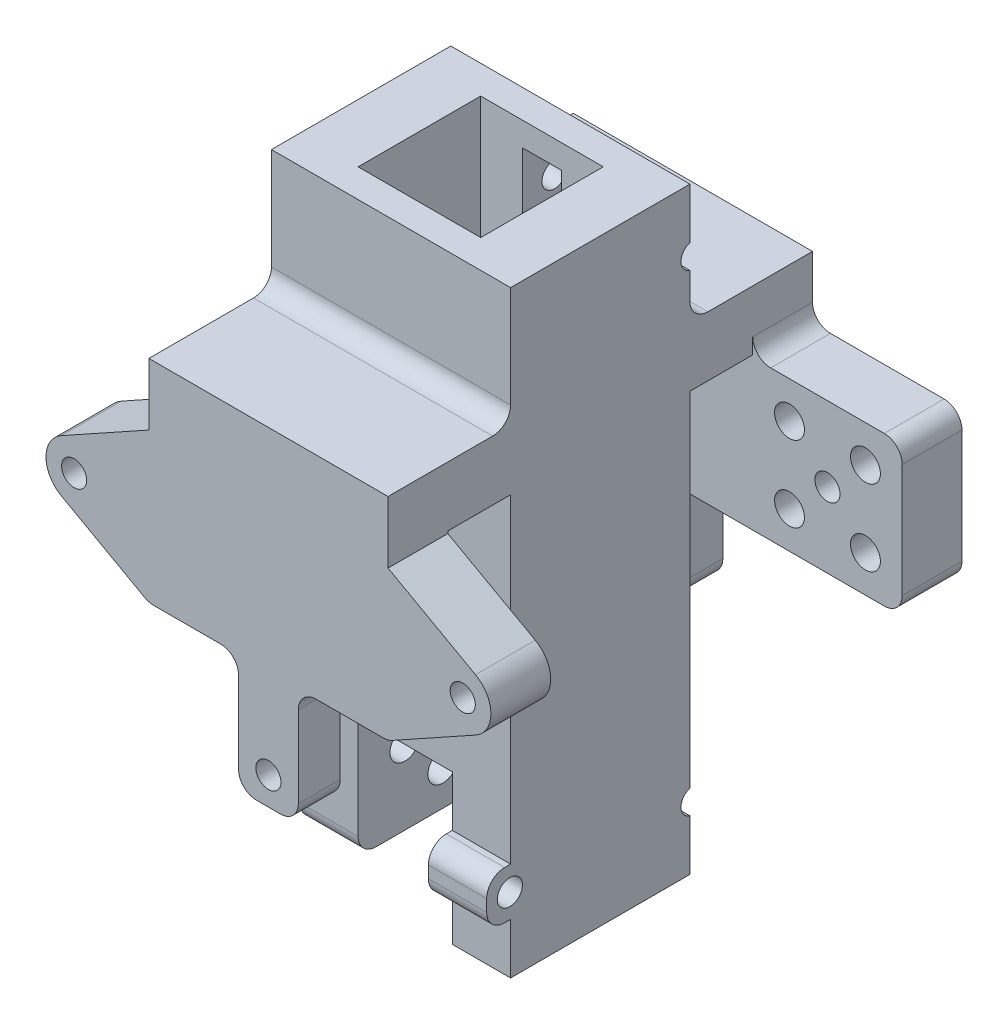
SolidWorks part; units mm, degrees
note: The reader was unsure of these and kept them because the rebuilt part matched: shared geometry of "Sketch25<3>".
ref_plane "Front Plane" through (0, 0, 0) normal (0, 0, 1) x (1, 0, 0)
ref_plane "Top Plane" through (0, 0, 0) normal (0, 1, 0) x (1, 0, 0)
ref_plane "Right Plane" through (0, 0, 0) normal (1, 0, 0) x (0, 0, -1)
sketch "Sketch2" plane through (0, 0, 0) normal (0, 1, 0) x (1, 0, 0)
  line L14 (-20, 15) -> (20, 15)
  line L15 (-20, 15) -> (-20, -15)
  line L16 (-20, -15) -> (20, -15)
  line L17 (20, 15) -> (20, -15)
  line L18 (-20, 15) -> (20, -15) construction
  line L19 (-20, -15) -> (20, 15) construction
  point P0 (0, 0)
  dimension "D1" = 40
  dimension "D2" = 30
extrude "Boss-Extrude1" add sketch "Sketch2" along normal blind 100
sketch "Sketch3" plane through (0, 0, 0) normal (0, 1, 0) x (1, 0, 0)
  line L1 (-10.25, 10.25) -> (10.25, 10.25)
  line L2 (-10.25, 10.25) -> (-10.25, -10.25)
  line L3 (-10.25, -10.25) -> (10.25, -10.25)
  line L4 (10.25, 10.25) -> (10.25, -10.25)
  line L5 (-10.25, 10.25) -> (10.25, -10.25) construction
  line L6 (-10.25, -10.25) -> (10.25, 10.25) construction
  point P0 (0, 0)
  dimension "D1" = 20.5
  dimension "D2" = 20.5
extrude "Cut-Extrude1" cut sketch "Sketch3" along normal blind 100
sketch "Sketch4" plane through (0, 0, 15) normal (0, 0, 1) x (1, 0, 0)
  line L1 (-10.25, -25) -> (10.25, -25)
  line L2 (-10.25, -25) -> (-10.25, 25)
  line L3 (-10.25, 25) -> (10.25, 25)
  line L4 (10.25, -25) -> (10.25, 25)
  line L5 (-10.25, -25) -> (10.25, 25) construction
  line L6 (-10.25, 25) -> (10.25, -25) construction
  point P0 (0, 0)
  dimension "D1" = 20.5
  dimension "D2" = 50
extrude "Cut-Extrude2" cut sketch "Sketch4" against normal up to surface (4.75 mm away) up to face at (0, 50, 10.25)
sketch "Sketch5" plane through (-10.25, 0, 0) normal (1, 0, 0) x (0, 0, -1)
  line L1 (-10.25, 25) -> (-15, 25)
  line L2 (-10.25, 25) -> (-10.25, 0)
  line L3 (-10.25, 0) -> (-15, 0)
  line L4 (-15, 25) -> (-15, 0)
extrude "Cut-Extrude4" cut sketch "Sketch5" against normal up to surface (9.75 mm away) up to face at (-20, 50, 0)
sketch "Sketch6" plane through (-20, 0, 0) normal (-1, 0, 0) x (0, 0, 1)
  line L0 (10.25, 12.5) -> (-15, 12.5) construction
  line L1 (10.25, 25) -> (10.25, 0) construction
  line L2 (-15, 100) -> (-15, 0) construction
  line L4 (10.25, 12.5) -> (15.125, 12.5) construction
  line L5 (-3.925, 12.5) -> (-3.925, 18.85) construction
  circle A0 centre (2.425, 12.5) radius 2.1
  circle A1 centre (-10.275, 12.5) radius 2.1
  circle A2 centre (-3.925, 18.85) radius 2.1
  circle A3 centre (-3.925, 6.15) radius 2.1
  dimension "D2" = 12.7
  dimension "D3" = 4.2
  dimension "D4" = 12.7
  dimension "D5" = 4.2
  dimension "D7" = 6.35
  dimension "D1" = 4.875
  dimension "D6" = 6.35
extrude "Cut-Extrude5" cut sketch "Sketch6" against normal up to surface (9.75 mm away) up to face at (-10.25, 45, 2.05)
sketch "Sketch7" plane through (-10.25, 0, 0) normal (1, 0, 0) x (0, 0, -1)
  circle A0 centre (-2.425, 12.5) radius 2.5
  circle A1 centre (10.275, 12.5) radius 2.5
  circle A2 centre (3.925, 18.85) radius 2.5
  circle A6 centre (3.925, 6.15) radius 2.5
  dimension "D1" = 12.7
extrude "Cut-Extrude6" cut sketch "Sketch7" against normal blind 5.18
sketch "Sketch8" plane through (0, 0, -15) normal (0, 0, -1) x (-1, 0, 0)
  line L0 (-20, 100) -> (-20, 0) construction
  line L1 (20, 100) -> (20, 0) construction
  line L2 (-20, 70) -> (20, 70)
  line L3 (-20, 70) -> (-20, 80)
  line L4 (-20, 80) -> (20, 80)
  line L5 (20, 70) -> (20, 80)
  line L6 (-20, 0) -> (20, 0) construction
  dimension "D1" = 70
  dimension "D2" = 10
extrude "Boss-Extrude2" add sketch "Sketch8" along normal blind 20.5
sketch "Sketch9" plane through (0, 70, 0) normal (0, -1, 0) x (1, 0, 0)
  line L0 (20, -35.5) -> (20, -15) construction
  line L1 (-20, -35.5) -> (20, -35.5)
  line L2 (-20, -35.5) -> (-20, -25.5)
  line L3 (-20, -25.5) -> (20, -25.5)
  line L4 (20, -35.5) -> (20, -25.5)
  dimension "D1" = 10
extrude "Boss-Extrude3" add sketch "Sketch9" along normal blind 45
sketch "Sketch10" plane through (0, 0, -35.5) normal (0, 0, -1) x (-1, 0, 0)
  line L0 (-20, 57.125) -> (20, 57.125) construction
  line L1 (-20, 80) -> (-20, 25) construction
  line L2 (20, 25) -> (20, 80) construction
  line L3 (20, 80) -> (-20, 80) construction
  dimension "D1" = 22.875
sketch "Sketch11" plane through (20, 0, 0) normal (1, 0, 0) x (0, 0, -1)
  line L5 (35.5, 57.125) -> (25.5, 57.125) construction
  line L6 (25.5, 25) -> (25.5, 70) construction
  line L7 (35.5, 80) -> (35.5, 25) construction
  line L8 (25.5, 69.625) -> (35.5, 69.625)
  line L9 (25.5, 69.625) -> (25.5, 44.625)
  line L10 (25.5, 44.625) -> (35.5, 44.625)
  line L11 (35.5, 69.625) -> (35.5, 44.625)
  dimension "D1" = 25
extrude "Boss-Extrude4" add sketch "Sketch11" along normal blind 25 and the other way offset from surface (65 mm away) 25 other way up to face at (-20, 12.5, 4.525)
sketch "Sketch13" plane through (0, 0, -35.5) normal (0, 0, -1) x (-1, 0, 0)
  line L0 (-45, 44.625) -> (-20, 69.625) construction
  line L1 (-20, 44.625) -> (-45, 69.625) construction
  circle A0 centre (-32.5, 57.125) radius 2.1
  circle A1 centre (-26.15, 63.475) radius 2.1
  circle A2 centre (-38.85, 63.475) radius 2.1
  circle A3 centre (-38.85, 50.775) radius 2.1
  circle A4 centre (-26.15, 50.775) radius 2.1
  dimension "D1" = 12.7
  dimension "D2" = 6.35
  dimension "D3" = 12.7
  dimension "D4" = 6.35
extrude "Cut-Extrude7" cut sketch "Sketch13" against normal blind 4.57
sketch "Sketch14" plane through (0, 0, -25.5) normal (0, 0, 1) x (1, 0, 0)
  circle A0 centre (32.5, 57.125) radius 2.1
  circle A1 centre (38.85, 63.475) radius 2.5
  circle A2 centre (26.15, 63.475) radius 2.5
  circle A3 centre (26.15, 50.775) radius 2.5
  circle A4 centre (38.85, 50.775) radius 2.5
extrude "Cut-Extrude8" cut sketch "Sketch14" against normal up to surface (5.43 mm away) up to face at (36.75, 63.475, -30.93)
sketch "Sketch15" plane through (0, 0, -35.5) normal (0, 0, -1) x (-1, 0, 0)
  line L0 (20, 44.625) -> (45, 69.625) construction
  line L1 (45, 44.625) -> (20, 69.625) construction
  line L2 (20, 69.625) -> (34.6326, 61.4958)
  line L3 (34.6326, 52.7542) -> (20, 44.625)
  line L4 (20, 44.625) -> (45, 44.625)
  line L5 (45, 44.625) -> (45, 69.625)
  line L6 (45, 69.625) -> (20, 69.625)
  line L7 (-20, 57.125) -> (20, 57.125) construction
  circle A0 centre (32.5, 57.125) radius 2.1
  arc A1 (34.6326, 52.7542) -> (34.6326, 61.4958) centre (32.2044, 57.125) ccw
  circle A2 centre (0, 29.65) radius 2.1
  point P13 (42.5, 57.125)
  dimension "D1" = 10
  dimension "D2" = 5
  dimension "D3" = 27.475
extrude "Cut-Extrude9" cut sketch "Sketch15" against normal up to surface (10 mm away) up to face at (41.35, 50.775, -25.5)
mirror "Mirror2" about plane through (0, 0, 0) normal (0, 0, 1) of "Cut-Extrude9", "Boss-Extrude2", "Boss-Extrude3", "Boss-Extrude4"
sketch "Sketch18" plane through (0, 0, 35.5) normal (0, 0, 1) x (1, 0, 0)
  line L0 (20, 44.625) -> (45, 44.625) construction
  line L1 (20, 69.625) -> (34.6326, 61.4958)
  line L2 (34.6326, 52.7542) -> (20, 44.625)
  line L3 (20, 44.625) -> (45, 44.625)
  line L4 (45, 44.625) -> (45, 69.625)
  line L5 (45, 69.625) -> (20, 69.625)
  line L6 (-20, 44.625) -> (20, 44.625) construction
  circle A0 centre (32.5, 57.125) radius 2.1
  arc A1 (34.6326, 61.4958) -> (34.6326, 52.7542) centre (32.2044, 57.125) cw
  point P16 (42.5, 57.125)
  point P25 (0, 29.65)
  line M12 (20, 44.625) -> (45, 44.625)
  line M13 (45, 44.625) -> (45, 69.625)
  line M14 (45, 69.625) -> (20, 69.625)
  dimension "D1" = 12.5
  dimension "D4" = 5
  dimension "D2" = 12.5
  dimension "D3" = 10
extrude "Cut-Extrude10" cut sketch "Sketch18" against normal up to surface (10 mm away) contours L1 A1 L2 M12 M13 M14 | A0
sketch "Sketch19" plane through (0, 0, 35.5) normal (0, 0, 1) x (1, 0, 0)
  line L0 (-20, 44.625) -> (20, 44.625) construction
  line L1 (-20, 25) -> (20, 25) construction
  line L2 (-5, 44.625) -> (5, 44.625)
  line L3 (-5, 44.625) -> (-5, 25)
  line L4 (-5, 25) -> (5, 25)
  line L5 (5, 44.625) -> (5, 25)
  circle A0 centre (0, 29.65) radius 2.1 construction
  line M4 (20, 25) -> (20, 44.625)
  line M14 (-20, 44.625) -> (-20, 25)
  line M15 (-20, 25) -> (20, 25)
  dimension "D2" = 5
  dimension "D1" = 10
extrude "Cut-Extrude11" cut sketch "Sketch19" along a picked direction on the side against the normal blind 12.57 contours L0 L3 M14 M15 | L0 L5 M15 M4
mirror "Mirror3" about plane through (0, 0, 0) normal (0, 0, 1) of "Cut-Extrude11"
fillet "Fillet1" radius 3 17 edges at (5, 25, 30.5) (-5, 25, 30.5) (-15.125, 0, 10.25) (20, 69.625, -30.5) (20, 44.625, 30.5) (5, 44.625, 30.5) (-20, 44.625, 30.5) (-5, 44.625, 30.5) (-20, 44.625, -30.5) (-5, 44.625, -30.5) (5, 44.625, -30.5) (45, 69.625, -30.5) (45, 44.625, -30.5) (-5, 25, -30.5) (5, 25, -30.5) (0, 80, -15) (0, 80, 15)
sketch "Sketch20" plane through (0, 0, 25.5) normal (0, 0, -1) x (-1, 0, 0)
  line L0 (-5, 28) -> (-5, 41.625) construction
  line L1 (-5, 40.086) -> (6.3149, 40.086)
  line L2 (-5, 40.086) -> (-5, 13.8516)
  line L3 (-5, 13.8516) -> (6.3149, 13.8516)
  line L4 (6.3149, 40.086) -> (6.3149, 13.8516)
extrude "Cut-Extrude12" cut sketch "Sketch20" against normal blind 3
mirror "Mirror4" about plane through (0, 0, 0) normal (0, 0, 1) of "Cut-Extrude12"
sketch "Sketch21" plane through (-20, 0, 0) normal (-1, 0, 0) x (0, 0, 1)
  circle A0 centre (15.125, 12.5) radius 2.1
  point P0 (2.425, 12.5)
  dimension "D1" = 12.7
sketch "Sketch22" plane through (0, 0, 15) normal (0, 0, 1) x (1, 0, 0)
  line L0 (10.25, 0) -> (10.25, 25) construction
  line L1 (10.25, 8.5) -> (20, 8.5)
  line L2 (10.25, 8.5) -> (10.25, 16.5)
  line L3 (10.25, 16.5) -> (20, 16.5)
  line L4 (20, 8.5) -> (20, 16.5)
  line L5 (20, 70) -> (20, 0) construction
  point P0 (-20, 12.5)
  dimension "D1" = 8
  dimension "D2" = 4
extrude "Boss-Extrude5" add sketch "Sketch22" along normal blind 4
extrude "Cut-Extrude13" cut sketch "Sketch21" against normal up to surface (40 mm away) up to face at (20, 59.0572, 3.0909)
fillet "Fillet2" radius 3 2 edges at (15.125, 8.5, 19) (15.125, 16.5, 19)
sketch "Sketch23" plane through (0, 0, -15) normal (0, 0, -1) x (-1, 0, 0)
  line L0 (-20, 100) -> (20, 100) construction
  line L1 (-3.25, 96) -> (3.25, 96)
  line L2 (-3.25, 96) -> (-3.25, 83)
  line L3 (-3.25, 83) -> (3.25, 83)
  line L4 (3.25, 96) -> (3.25, 83)
  line L5 (-3.25, 96) -> (3.25, 83) construction
  line L6 (-3.25, 83) -> (3.25, 96) construction
  line L7 (-20, 0) -> (20, 0) construction
  line L8 (-3.25, 17) -> (3.25, 17)
  line L9 (-3.25, 17) -> (-3.25, 4)
  line L10 (-3.25, 4) -> (3.25, 4)
  line L11 (3.25, 17) -> (3.25, 4)
  line L12 (-3.25, 17) -> (3.25, 4) construction
  line L13 (-3.25, 4) -> (3.25, 17) construction
  line L16 (-20, 100) -> (-20, 83) construction
  line L18 (20, 70) -> (20, 0) construction
  point P0 (0, 89.5)
  point P7 (0, 10.5)
  dimension "D1" = 6.5
  dimension "D2" = 13
  dimension "D3" = 4
  dimension "D4" = 13
  dimension "D5" = 6.5
  dimension "D6" = 4
  dimension "D7" = 20
  dimension "D8" = 20
extrude "Cut-Extrude14" cut sketch "Sketch23" against normal up to surface (4.75 mm away) up to face at (-3.4167, 37.5, -10.25)
sketch "Sketch25" plane through (3.25, 0, 0) normal (-1, 0, 0) x (0, 0, 1)
  line L0 (-10.25, 96) -> (-15, 96) construction
  line L1 (-15, 96) -> (-15, 83) construction
  line L2 (-10.25, 4) -> (-15, 4) construction
  line L3 (-15, 17) -> (-15, 4) construction
  circle A0 centre (-15.6, 89.5) radius 2.1
  circle A1 centre (-15.6, 89.5) radius 3.1
  circle A2 centre (-15.6, 10.5) radius 2.1
  circle A3 centre (-15.6, 10.5) radius 3.1
  line M4 (-15, 96) -> (-15, 83)
  dimension "D1" = 6.5
  dimension "D3" = 6.5
  dimension "D2" = 0.6
  dimension "D4" = 0.6
extrude "Boss-Extrude7" add sketch "Sketch25" against normal blind 4
extrude "Cut-Extrude16" cut sketch "Sketch25<3>" against normal blind 16.75 contours A2 | A0 M4
sketch "Sketch25<3>" plane through (3.25, 0, 0) normal (-1, 0, 0) x (0, 0, 1) same geometry as "Sketch25"
mirror "Mirror5" about plane through (0, 0, 0) normal (1, 0, 0) of "Cut-Extrude16", "Boss-Extrude7"
